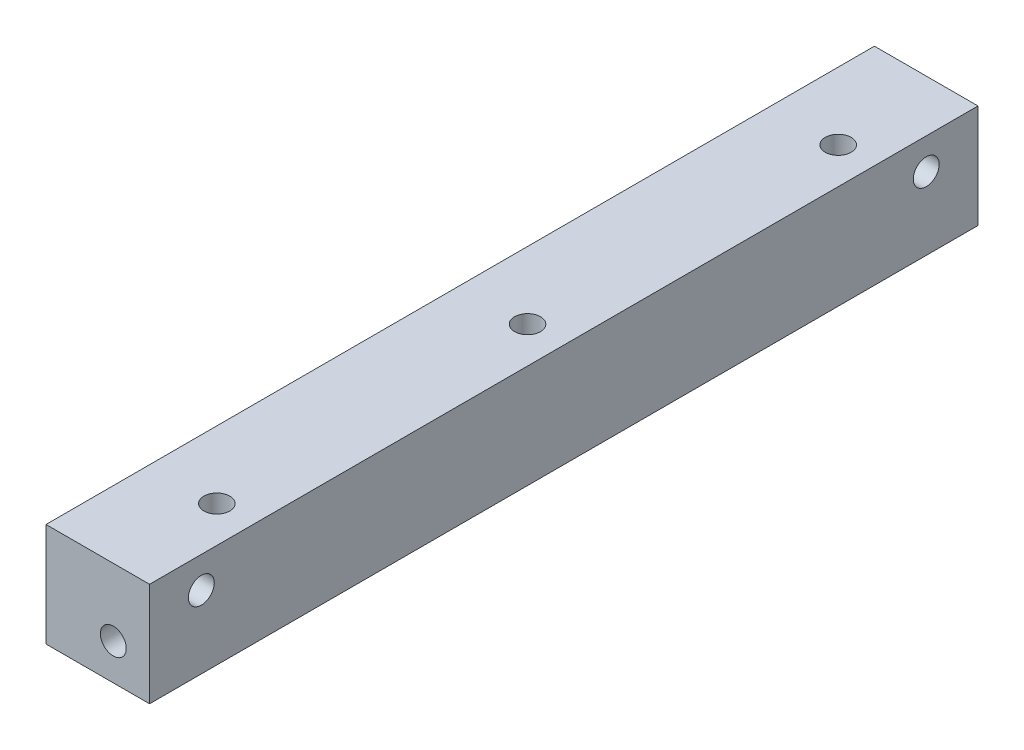
SolidWorks part; units mm, degrees
ref_plane "Ön Düzlem" through (0, 0, 0) normal (0, 0, 1) x (1, 0, 0)
ref_plane "Üst Düzlem" through (0, 0, 0) normal (0, 1, 0) x (1, 0, 0)
ref_plane "Sağ Düzlem" through (0, 0, 0) normal (1, 0, 0) x (0, 0, -1)
sketch "Çizim1" plane through (0, 0, 0) normal (0, 0, 1) x (1, 0, 0)
  line L0 (0, 20) -> (20, 0) construction
  line L1 (0, 0) -> (20, 0)
  line L2 (0, 0) -> (0, 20)
  line L3 (0, 20) -> (20, 20)
  line L4 (20, 0) -> (20, 20)
  line L5 (20, 20) -> (0, 0) construction
  point P4 (10, 10)
extrude "Yükseklik-Ekstrüzyon1" add sketch "Çizim1" along normal blind 160
sketch "Çizim2" plane through (0, 0, 0) normal (-1, 0, 0) x (0, 0, 1)
  line L0 (20, 0) -> (20, 20) construction
  line L1 (160, 0) -> (0, 0) construction
  line L2 (160, 20) -> (0, 20) construction
  line L3 (80, 0) -> (80, 20) construction
  line L4 (140, 0) -> (140, 20) construction
  line L5 (0, 20) -> (0, 0) construction
  line L6 (160, 20) -> (160, 0) construction
  line L7 (0, 7) -> (160, 7) construction
  point P16 (20, 7)
  point P17 (80, 7)
  point P18 (140, 7)
  dimension "D1" = 20
  dimension "D2" = 20
  dimension "D3" = 7
hole_wizard "Ø4.0mm Saplama Delikleri3" positions "3B Çizim1" profile "Çizim3" hole size "Ø4.0" standard "ANSI Metric"
sketch3d "3B Çizim1"
  point P0 (0, 7, 20)
  point P3 (0, 7, 80)
  point P6 (0, 7, 140)
sketch "Çizim3" plane through (0, 7, 20) normal (0, 1, 0) x (0, 0, 1)
  line L0 (0, 0) -> (0, 10)
  line L1 (0, 10) -> (2.5, 10)
  line L2 (2.5, 10) -> (2.5, 0)
  line L5 (2.5, 0) -> (0, 0)
  line L10 (0, 10) -> (-2.5, 10) construction
  line L11 (0, -6.35) -> (0, 107.95) construction
  dimension "Hole Dia." = 5
  dimension "Hole Depth" = 10
  dimension "Drill Angle" = 180
sketch "Çizim4" plane through (0, 20, 0) normal (0, 1, 0) x (1, 0, 0)
  line L0 (13, 0) -> (13, -160) construction
  line L1 (20, 0) -> (0, 0) construction
  line L2 (20, -160) -> (0, -160) construction
  line L3 (20, -160) -> (20, 0) construction
  line L4 (0, -20) -> (20, -20) construction
  line L5 (0, -80) -> (20, -80) construction
  line L6 (0, 0) -> (0, -160) construction
  line L7 (0, -140) -> (20, -140) construction
  point P19 (13, -20)
  point P20 (13, -80)
  point P21 (13, -140)
  dimension "D1" = 7
hole_wizard "Ø4.0mm Saplama Delikleri4" positions "3B Çizim2" profile "Çizim5" hole size "Ø4.0" standard "ANSI Metric"
sketch3d "3B Çizim2"
  point P0 (13, 20, 20)
  point P3 (13, 20, 80)
  point P6 (13, 20, 140)
sketch "Çizim5" plane through (13, 20, 20) normal (1, 0, 0) x (0, 0, 1)
  line L0 (0, 0) -> (0, 10)
  line L1 (0, 10) -> (2.5, 10)
  line L2 (2.5, 10) -> (2.5, 0)
  line L5 (2.5, 0) -> (0, 0)
  line L10 (0, 10) -> (-2.5, 10) construction
  line L11 (0, -6.35) -> (0, 107.95) construction
  dimension "Hole Dia." = 5
  dimension "Hole Depth" = 10
  dimension "Drill Angle" = 180
sketch "Çizim13" plane through (0, 0, 160) normal (0, 0, 1) x (1, 0, 0)
  line L0 (13, 20) -> (13, 0) construction
  line L1 (0, 0) -> (20, 0) construction
  line L2 (0, 7) -> (20, 7) construction
  line L3 (20, 0) -> (20, 20) construction
  circle A0 centre (13, 7) radius 2.5
extrude "Kes-Ekstrüzyon1" cut sketch "Çizim13" against normal blind 10
sketch "Çizim15" plane through (0, 0, 0) normal (0, 0, -1) x (-1, 0, 0)
  line L0 (-13, 20) -> (-13, 0) construction
  line L1 (0, 0) -> (-20, 0) construction
  line L2 (0, 7) -> (-20, 7) construction
  line L3 (-20, 0) -> (-20, 20) construction
  circle A0 centre (-13, 7) radius 2.5
extrude "Kes-Ekstrüzyon2" cut sketch "Çizim15" against normal blind 10
sketch "Çizim18" plane through (20, 0, 0) normal (1, 0, 0) x (0, 0, -1)
  line L0 (0, 0) -> (0, 20) construction
  line L1 (0, 20) -> (-160, 20) construction
  line L2 (-160, 0) -> (-160, 20) construction
  circle A0 centre (-10, 14) radius 2.5
  circle A1 centre (-150, 14) radius 2.5
  dimension "D1" = 10
  dimension "D2" = 6
  dimension "D3" = 10
  dimension "D4" = 6
extrude "Kes-Ekstrüzyon3" cut sketch "Çizim18" against normal blind 10
sketch "Çizim20" plane through (0, 0, 0) normal (0, -1, 0) x (1, 0, 0)
  line L0 (0, 0) -> (0, 160) construction
  line L1 (0, 0) -> (20, 0) construction
  line L2 (0, 160) -> (20, 160) construction
  circle A0 centre (6, 10) radius 2.5
  circle A1 centre (6, 150) radius 2.5
  dimension "D1" = 6
  dimension "D2" = 10
  dimension "D3" = 6
  dimension "D4" = 10
extrude "Kes-Ekstrüzyon4" cut sketch "Çizim20" against normal blind 10
